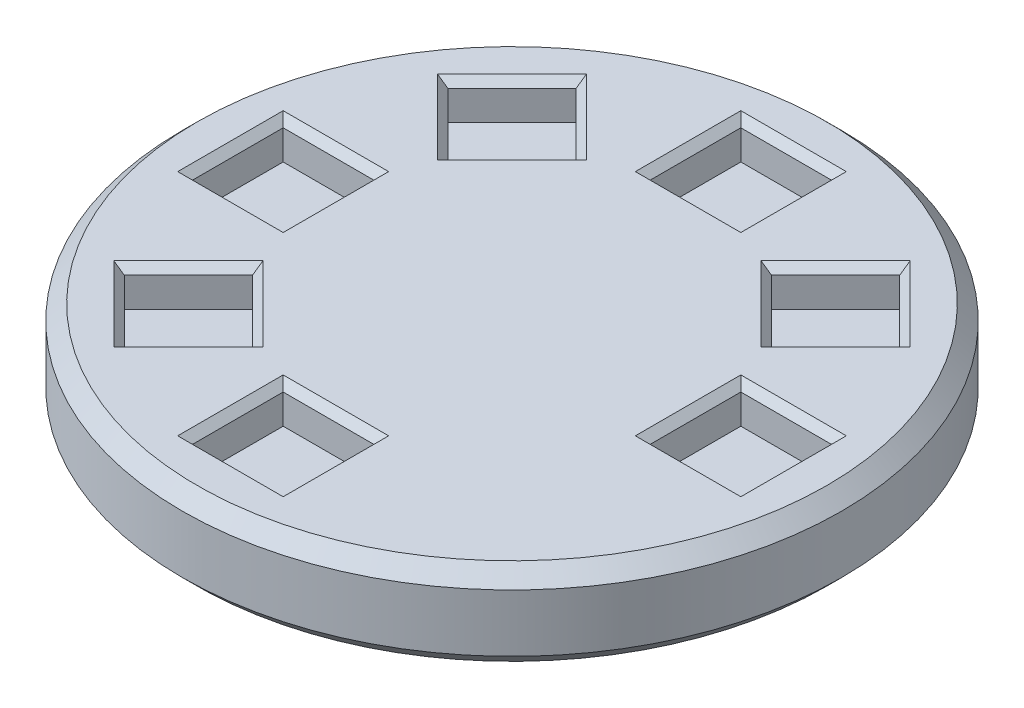
SolidWorks part; units mm, degrees
ref_plane "Front Plane" through (0, 0, 0) normal (0, 0, 1) x (1, 0, 0)
ref_plane "Top Plane" through (0, 0, 0) normal (0, 1, 0) x (1, 0, 0)
ref_plane "Right Plane" through (0, 0, 0) normal (1, 0, 0) x (0, 0, -1)
sketch "Sketch1" plane through (0, 0, 0) normal (0, 0, 1) x (1, 0, 0)
  line L0 (0, -2049.5716) -> (0, 100429.0072) construction
  line L1 (0, -32.3461) -> (9.2022, -32.3461)
  line L2 (9.2022, -32.3461) -> (9.2022, -11.7666)
  line L3 (9.2022, -11.7666) -> (44.5385, -11.7666)
  line L4 (44.5385, -11.7666) -> (44.5385, 0)
  line L5 (44.5385, 0) -> (0, 0)
  line L6 (0, 0) -> (0, -32.3461)
  point P8 (24.7863, 0)
  point P10 (30.9113, 0)
  point P13 (37.0363, 0)
  dimension "D1" = 12.25
  dimension "D2" = 6.125
revolve "Revolve1" add sketch "Sketch1" angle 360 about L0
sketch "Sketch3" plane through (0, 0, 0) normal (0, 1, 0) x (1, 0, 0)
  line L0 (7.1217, 0) -> (44.5385, 0) construction
  line L1 (24.7863, 6.125) -> (37.0363, 6.125)
  line L2 (24.7863, 6.125) -> (24.7863, -6.125)
  line L3 (24.7863, -6.125) -> (37.0363, -6.125)
  line L4 (37.0363, 6.125) -> (37.0363, -6.125)
  point P9 (37.0363, 0)
extrude "Cut-Extrude1" cut sketch "Sketch3" against normal blind 5
chamfer "Chamfer1" distance 1 angle 45 4 edges at (37.0363, 0, 0) (30.9113, 0, 6.125) (24.7863, 0, 0) (30.9113, 0, -6.125)
pattern_circular "CirPattern1" count 8 over 360 about axis through (0, -2049.5716, 0) along (0, 1, 0) skipping 7 of "Cut-Extrude1", "Chamfer1"
ref_axis "Rotor Axis" through (0, -2049.5716, 0) along (0, 1, 0)
chamfer "Chamfer2" distance 2 angle 45 1 edges at (9.2022, -32.3461, 0)
chamfer "Chamfer3" distance 2 angle 45 2 edges at (44.5385, -11.7666, 0) (44.5385, 0, 0)
equation "\"D2@Sketch1\"=\"D1@Sketch1\"/2"
